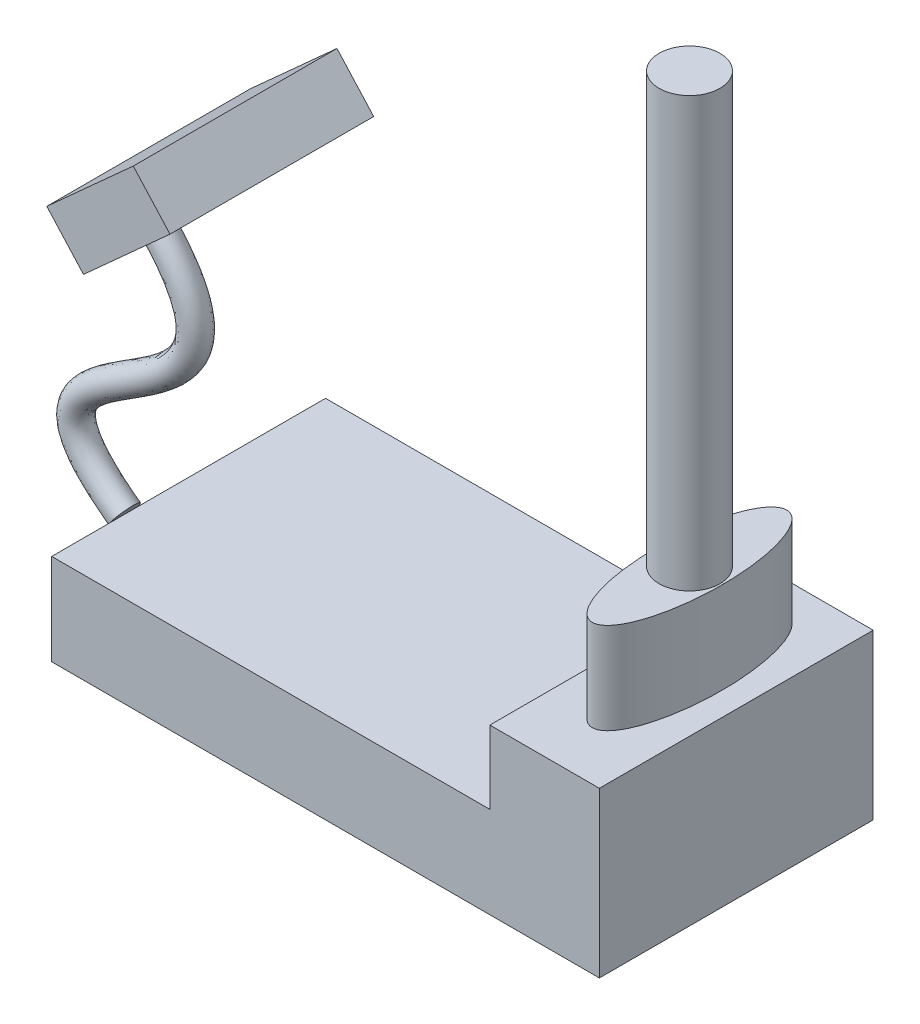
SolidWorks part; units mm, degrees
ref_plane "Front Plane" through (0, 0, 0) normal (0, 0, 1) x (1, 0, 0)
ref_plane "Top Plane" through (0, 0, 0) normal (0, 1, 0) x (1, 0, 0)
ref_plane "Right Plane" through (0, 0, 0) normal (1, 0, 0) x (0, 0, -1)
sketch "Sketch2" plane through (0, 0, 0) normal (0, 1, 0) x (1, 0, 0)
  line L1 (0, 0) -> (76.2, 0)
  line L2 (0, 0) -> (0, 38.1)
  line L3 (0, 38.1) -> (76.2, 38.1)
  line L4 (76.2, 0) -> (76.2, 38.1)
extrude "Boss-Extrude1" add sketch "Sketch2" along normal blind 12.7
sketch "Sketch4" plane through (0, 12.7, 0) normal (0, 1, 0) x (1, 0, 0)
  line L5 (0, 0) -> (76.2, 0) construction
  line L6 (76.2, 38.1) -> (60.9634, 38.1)
  line L7 (76.2, 38.1) -> (76.2, 0)
  line L8 (76.2, 0) -> (60.9634, 0)
  line L9 (60.9634, 38.1) -> (60.9634, 0)
extrude "Boss-Extrude2" add sketch "Sketch4" along normal blind 10.16
sketch3d "3DSketch1" plane through (0, 0, 0) normal (0, 0, 1) x (1, 0, 0)
  dimension "D1" = 10.16
sketch "Sketch5" plane through (0, 0, -10.16) normal (0, 0, 1) x (1, 0, 0)
  spline S0 degree 3 poles (0, 12.7487) (-23.8545, 30.0744) (24.4606, 27.7581) (5.1142, 49.1778) knots 0 0 0 0 1 1 1 1
sketch "Sketch39" plane through (0, 22.86, 0) normal (0, 1, 0) x (1, 0, 0)
  ellipse E0 centre (68.4091, 20.3313) end of major axis (68.4091, 33.8581) minor radius 4.5227
extrude "Boss-Extrude5" add sketch "Sketch39" along normal blind 12.7
sketch "Sketch40" plane through (0, 35.56, 0) normal (0, 1, 0) x (1, 0, 0)
  circle A0 centre (68.4091, 20.3313) radius 4.2309
extrude "Boss-Extrude6" add sketch "Sketch40" along normal blind 59.69
sketch3d "3DSketch2" plane through (0, 0, 0) normal (0, 0, 1) x (1, 0, 0)
sweep "Sweep1" add path "Sketch5" circular profile diameter 3.81 parameters "D3"=3.81
sketch "Sketch65" plane through (-22.1644, 24.5396, 0) normal (-0.6703, 0.7421, 0) x (0.7421, 0.6703, 0)
  line L1 (47.4201, 31.7739) -> (31.2043, 31.7739)
  line L2 (47.4201, 31.7739) -> (47.4201, 3.4315)
  line L3 (47.4201, 3.4315) -> (31.2043, 3.4315)
  line L4 (31.2043, 31.7739) -> (31.2043, 3.4315)
  line L5 (47.4201, 31.7739) -> (31.2043, 3.4315) construction
  line L6 (47.4201, 3.4315) -> (31.2043, 31.7739) construction
  point P0 (39.3122, 17.6027)
extrude "Boss-Extrude7" add sketch "Sketch65" along normal blind 7.62
